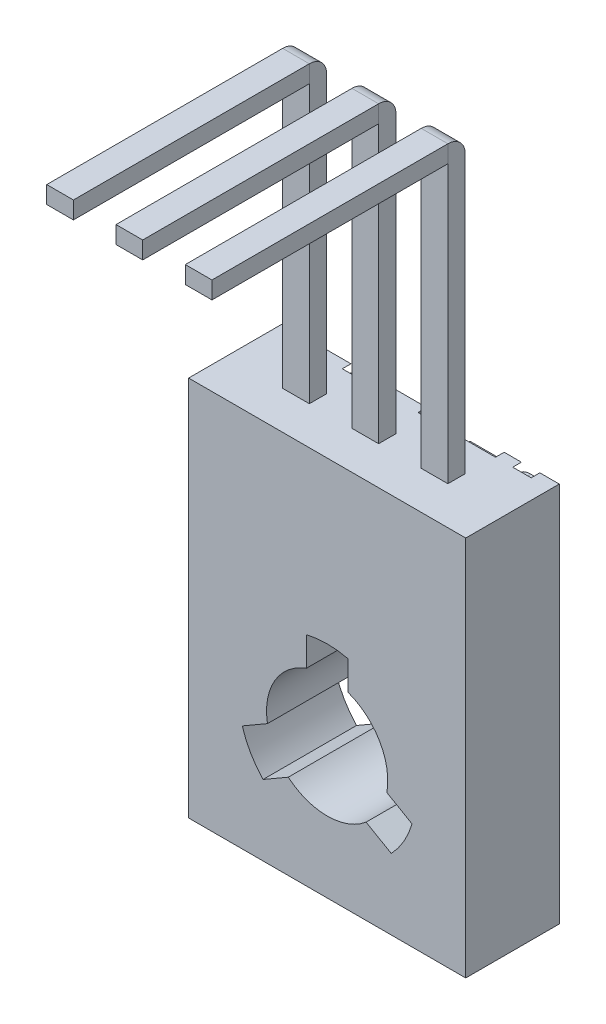
SolidWorks part; units mm, degrees
ref_plane "Front Plane" through (0, 0, 0) normal (0, 0, 1) x (1, 0, 0)
ref_plane "Top Plane" through (0, 0, 0) normal (0, 1, 0) x (1, 0, 0)
ref_plane "Right Plane" through (0, 0, 0) normal (1, 0, 0) x (0, 0, -1)
sketch "Sketch1" plane through (0, 0, 0) normal (0, 0, 1) x (1, 0, 0)
  line L1 (-4, 5.5) -> (4, 5.5)
  line L2 (-4, 5.5) -> (-4, -5.5)
  line L3 (-4, -5.5) -> (4, -5.5)
  line L4 (4, 5.5) -> (4, -5.5)
  line L5 (-4, 5.5) -> (4, -5.5) construction
  line L6 (-4, -5.5) -> (4, 5.5) construction
  circle A0 centre (0, -1.7) radius 2.555
  point P0 (0, 0)
  dimension "D3" = 5.11
  dimension "D1" = 11
  dimension "D2" = 8
  dimension "D4" = 3.8
extrude "Boss-Extrude1" add sketch "Sketch1" along normal mid plane 2.7
sketch "Sketch2" plane through (0, 5.5, 0) normal (0, 1, 0) x (1, 0, 0)
  line L0 (0, 0.8819) -> (0, -0.7814) construction
  line L1 (-0.385, 0.25) -> (0.385, 0.25)
  line L2 (-0.385, 0.25) -> (-0.385, -0.25)
  line L3 (-0.385, -0.25) -> (0.385, -0.25)
  line L4 (0.385, 0.25) -> (0.385, -0.25)
  line L5 (-0.385, 0.25) -> (0.385, -0.25) construction
  line L6 (-0.385, -0.25) -> (0.385, 0.25) construction
  line L7 (-2.385, 0.25) -> (-1.615, 0.25)
  line L8 (-2.385, 0.25) -> (-2.385, -0.25)
  line L9 (-2.385, -0.25) -> (-1.615, -0.25)
  line L10 (-1.615, 0.25) -> (-1.615, -0.25)
  line L11 (-2.385, 0.25) -> (-1.615, -0.25) construction
  line L12 (-2.385, -0.25) -> (-1.615, 0.25) construction
  line L13 (2.385, -0.25) -> (1.615, -0.25)
  line L14 (1.615, 0.25) -> (1.615, -0.25)
  line L15 (2.385, 0.25) -> (1.615, 0.25)
  line L16 (2.385, 0.25) -> (2.385, -0.25)
  point P0 (0, 0)
  point P7 (-2, 0)
  dimension "D1" = 0.5
  dimension "D2" = 0.77
  dimension "D3" = 0.77
  dimension "D4" = 0.5
  dimension "D5" = 2
extrude "Boss-Extrude2" add sketch "Sketch2" along normal blind 8
sketch "Sketch4" plane through (0, 0, 1.35) normal (0, 0, 1) x (1, 0, 0)
  line L0 (0, 0.8936) -> (0, -1.7) construction
  line L3 (-0.6, 0.8232) -> (-0.6, -0.0561)
  line L4 (0.6, 0.8232) -> (0.6, -0.0561)
  line L5 (2.4852, -2.442) -> (1.7237, -2.0023)
  line L6 (1.8852, -3.4812) -> (1.1237, -3.0416)
  line L7 (-1.8852, -3.4812) -> (-1.1237, -3.0416)
  line L8 (-2.4852, -2.442) -> (-1.7237, -2.0023)
  arc A0 (-1.1237, -3.0416) -> (1.1237, -3.0416) centre (0, -1.7) ccw
  arc A1 (-1.8852, -3.4812) -> (1.8852, -3.4812) centre (0, -1.7) ccw
  arc A2 (-0.6, -0.0561) -> (-1.7237, -2.0023) centre (0, -1.7) ccw
  arc A3 (-0.6, 0.8232) -> (-2.4852, -2.442) centre (0, -1.7) ccw
  arc A4 (1.7237, -2.0023) -> (0.6, -0.0561) centre (0, -1.7) ccw
  arc A5 (2.4852, -2.442) -> (0.6, 0.8232) centre (0, -1.7) ccw
  point P22 (0, -1.7)
  dimension "D1" = 3.5
  dimension "D2" = 0.6
  dimension "D3" = 3
extrude "Boss-Extrude3" add sketch "Sketch4" against normal up to surface (2.7 mm away) up to face at (0, 0, -1.35)
sketch "Sketch5" plane through (0, 0, -1.35) normal (0, 0, -1) x (-1, 0, 0)
  text T0 "TO126" font "Century Gothic" height in points 8
extrude "Cut-Extrude1" cut sketch "Sketch5" against normal blind 0.25
sketch "Sketch6" plane through (0, 13.5, 0) normal (0, 1, 0) x (1, 0, 0)
  line L0 (2.385, -0.25) -> (2.385, 0.25) construction
  line L1 (2.385, 0.25) -> (1.615, 0.25) construction
  line L2 (1.615, 0.25) -> (1.615, -0.25) construction
  line L3 (1.615, -0.25) -> (2.385, -0.25) construction
  line L4 (0.385, -0.25) -> (0.385, 0.25) construction
  line L5 (0.385, 0.25) -> (-0.385, 0.25) construction
  line L6 (-0.385, 0.25) -> (-0.385, -0.25) construction
  line L7 (-0.385, -0.25) -> (0.385, -0.25) construction
  line L8 (-1.615, -0.25) -> (-1.615, 0.25) construction
  line L9 (-1.615, 0.25) -> (-2.385, 0.25) construction
  line L10 (-2.385, 0.25) -> (-2.385, -0.25) construction
  line L11 (-2.385, -0.25) -> (-1.615, -0.25) construction
  line L12 (2.385, -0.25) -> (2.385, 0.25)
  line L13 (2.385, 0.25) -> (1.615, 0.25)
  line L14 (1.615, 0.25) -> (1.615, -0.25)
  line L15 (1.615, -0.25) -> (2.385, -0.25)
  line L16 (0.385, -0.25) -> (0.385, 0.25)
  line L17 (0.385, 0.25) -> (-0.385, 0.25)
  line L18 (-0.385, 0.25) -> (-0.385, -0.25)
  line L19 (-0.385, -0.25) -> (0.385, -0.25)
  line L20 (-1.615, -0.25) -> (-1.615, 0.25)
  line L21 (-1.615, 0.25) -> (-2.385, 0.25)
  line L22 (-2.385, 0.25) -> (-2.385, -0.25)
  line L23 (-2.385, -0.25) -> (-1.615, -0.25)
sketch "Sketch7" plane through (0, 0, 0) normal (1, 0, 0) x (0, 0, -1)
  line L0 (-0.25, 13.75) -> (-7.0608, 13.75)
  line L1 (0.25, 13.5) -> (-0.25, 13.5) construction
  line L2 (-0.25, 13.5) -> (-0.25, 5.5) construction
  line L3 (0, 13.5) -> (0, 18.5) construction
  arc A1 (0, 13.5) -> (-0.25, 13.75) centre (-0.25, 13.5) ccw
  point P1 (-1.3888, 14.9524)
  point P4 (-7.0856, 15.0611)
  point P7 (-0.2748, 10.2748)
  point P8 (0.0102, 14.4)
  point P10 (0.6377, 15.0377)
  dimension "D2" = 5
sweep "Sweep1" add profiles "Sketch6" path "Sketch7"
